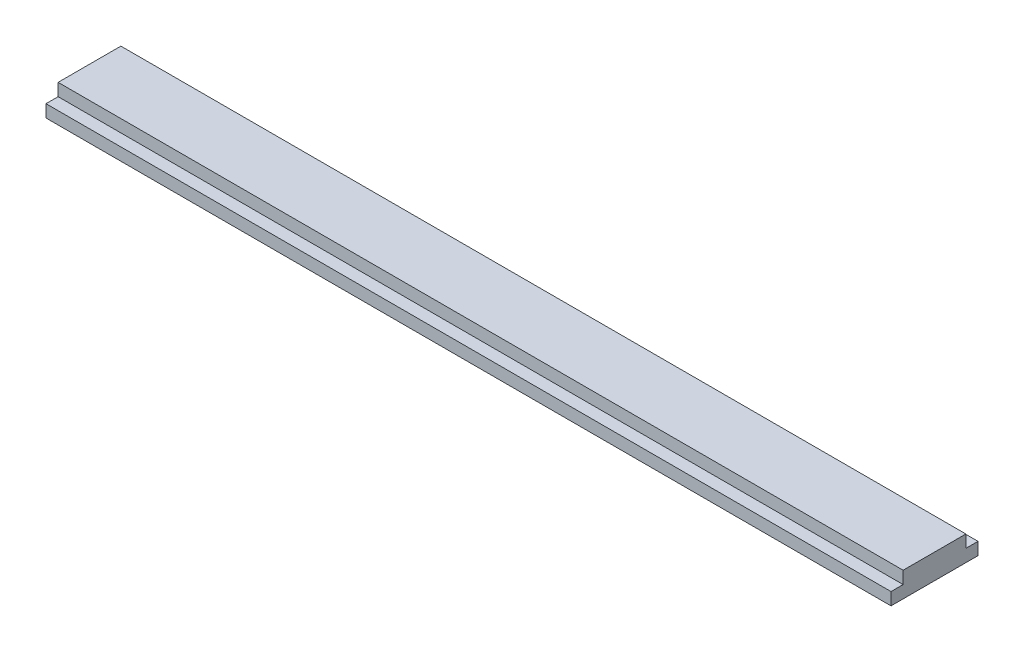
SolidWorks part; units mm, degrees
ref_plane "Front Plane" through (0, 0, 0) normal (0, 0, 1) x (1, 0, 0)
ref_plane "Top Plane" through (0, 0, 0) normal (0, 1, 0) x (1, 0, 0)
ref_plane "Right Plane" through (0, 0, 0) normal (1, 0, 0) x (0, 0, -1)
sketch "Sketch2" plane through (0, 0, 0) normal (0, 1, 0) x (1, 0, 0)
  line L5 (-68, 7) -> (68, 7)
  line L10 (-68, 7) -> (-68, -7)
  line L11 (-68, -7) -> (68, -7)
  line L12 (68, 7) -> (68, -7)
  line L13 (-68, 7) -> (68, -7) construction
  line L14 (-68, -7) -> (68, 7) construction
  line L15 (-68, 5.05) -> (68, 5.05)
  line L16 (-68, 5.05) -> (-68, -5.05)
  line L17 (-68, -5.05) -> (68, -5.05)
  line L18 (68, 5.05) -> (68, -5.05)
  line L19 (-68, 5.05) -> (68, -5.05) construction
  line L20 (-68, -5.05) -> (68, 5.05) construction
  point P0 (0, 0)
  point P5 (0, 0)
  dimension "D1" = 136
  dimension "D2" = 14
  dimension "D3" = 1.95
  dimension "D4" = 10.1
extrude "Middle Extrude" add sketch "Sketch2" along normal blind 4 contours L10 L17 L12 L15 region at (0, 0, 0)
extrude "Main Extrude" add sketch "Sketch2<4>" along normal blind 2 contours L17 L10 L11 L12 | L10 L15 L12 L5 region at (0, 0, -6.025) region at (0, 0, 6.025)
sketch "Sketch2<4>" plane through (0, 0, 0) normal (0, 1, 0) x (1, 0, 0) same geometry as "Sketch2"
